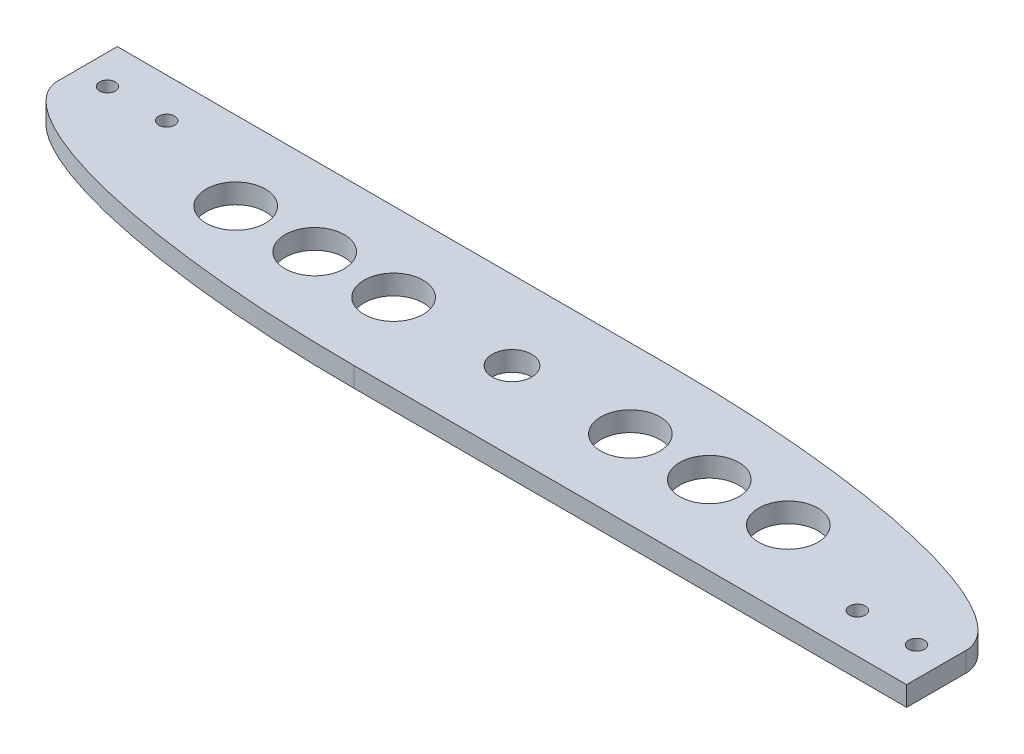
SolidWorks part; units mm, degrees
material "6061 Alloy"
ref_plane "Front Plane" through (0, 0, 0) normal (0, 0, 1) x (1, 0, 0)
ref_plane "Top Plane" through (0, 0, 0) normal (0, 1, 0) x (1, 0, 0)
ref_plane "Right Plane" through (0, 0, 0) normal (1, 0, 0) x (0, 0, -1)
sketch "Sketch2" plane through (0, 0, 0) normal (0, 1, 0) x (1, 0, 0)
  line L0 (0, 99.4411) -> (0, -82.6348) construction
  line L1 (-152.4, -25.4) -> (152.4, -25.4)
  line L2 (-152.4, -25.4) -> (-152.4, 25.4)
  line L3 (-152.4, 25.4) -> (152.4, 25.4)
  line L4 (152.4, -25.4) -> (152.4, 25.4)
  line L5 (-152.4, -25.4) -> (152.4, 25.4) construction
  line L6 (-152.4, 25.4) -> (152.4, -25.4) construction
  circle A0 centre (0, 0) radius 6.35
  circle A1 centre (-38.1, 0) radius 9.525
  circle A2 centre (-63.5, 0) radius 9.525
  circle A5 centre (-88.9, 0) radius 9.525
  circle A6 centre (38.1, 0) radius 9.525
  circle A7 centre (63.5, 0) radius 9.525
  circle A8 centre (88.9, 0) radius 9.525
  circle A9 centre (142.875, -12.7) radius 2.5527
  circle A10 centre (123.825, -12.7) radius 2.5527
  circle A11 centre (-142.875, 12.7) radius 2.5527
  circle A12 centre (-123.825, 12.7) radius 2.5527
  point P0 (0, 0)
  dimension "D3" = 12.7
  dimension "D4" = 19.05
  dimension "D8" = 5.1054
  dimension "D15" = 5.1054
  dimension "D1" = 304.8
  dimension "D2" = 50.8
  dimension "D5" = 38.1
  dimension "D6" = 25.4
  dimension "D7" = 25.4
  dimension "D9" = 9.525
  dimension "D10" = 19.05
  dimension "D11" = 12.7
  dimension "D12" = 9.525
  dimension "D13" = 19.05
  dimension "D14" = 12.7
extrude "Boss-Extrude2" add sketch "Sketch2" along normal mid plane 6.35
fillet "Fillet1" radius 31.75 2 edges at (152.4, 0, -25.4) (-152.4, 0, 25.4) second distance 127 first distance on face at (152.4, 0, 0) first distance on face at (-152.4, 0, 0)
